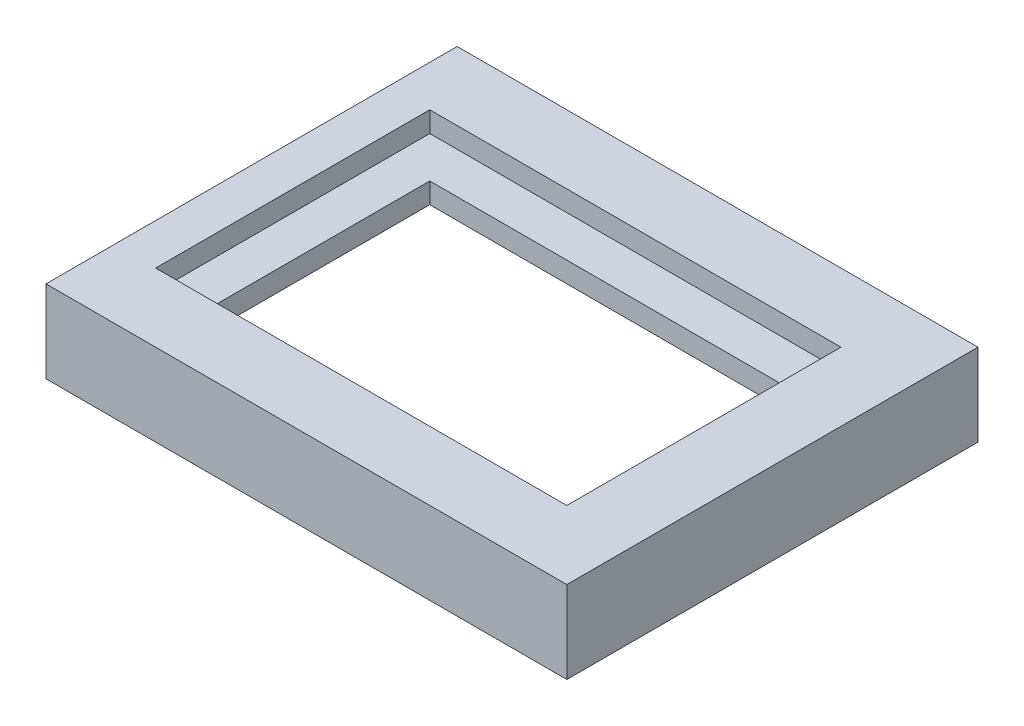
SolidWorks part; units mm, degrees
ref_plane "Front Plane" through (0, 0, 0) normal (0, 0, 1) x (1, 0, 0)
ref_plane "Top Plane" through (0, 0, 0) normal (0, 1, 0) x (1, 0, 0)
ref_plane "Right Plane" through (0, 0, 0) normal (1, 0, 0) x (0, 0, -1)
sketch "Sketch1" plane through (0, 0, 0) normal (0, 1, 0) x (1, 0, 0)
  line L1 (-9, -6.5) -> (9, -6.5)
  line L2 (-9, -6.5) -> (-9, 6.5)
  line L3 (-9, 6.5) -> (9, 6.5)
  line L4 (9, -6.5) -> (9, 6.5)
  line L5 (-9, -6.5) -> (9, 6.5) construction
  line L6 (-9, 6.5) -> (9, -6.5) construction
  line L7 (-10, -7.5) -> (10, -7.5)
  line L8 (-10, -7.5) -> (-10, 7.5)
  line L9 (-10, 7.5) -> (10, 7.5)
  line L10 (10, -7.5) -> (10, 7.5)
  line L11 (-10, -7.5) -> (10, 7.5) construction
  line L12 (-10, 7.5) -> (10, -7.5) construction
  point P0 (0, 0)
  point P6 (0, 0)
  dimension "D1" = 18
  dimension "D2" = 13
  dimension "D3" = 20
  dimension "D4" = 15
extrude "Boss-Extrude3" add sketch "Sketch1" along normal blind 3 contours L7 L10 L9 L8
sketch "Sketch4" plane through (-10, 0, 0) normal (-1, 0, 0) x (0, 0, 1)
  line L0 (-7.5, 1.5) -> (7.5, 1.5)
  line L1 (-7.5, 3) -> (-7.5, 0) construction
  line L2 (7.5, 3) -> (7.5, 0) construction
  line L4 (-6.5, 0.75) -> (6.5, 0.75)
  line L5 (-6.5, 0.75) -> (-6.5, 2.25)
  line L6 (-6.5, 2.25) -> (6.5, 2.25)
  line L7 (6.5, 0.75) -> (6.5, 2.25)
  line L8 (-6.5, 0.75) -> (6.5, 2.25) construction
  line L9 (-6.5, 2.25) -> (6.5, 0.75) construction
  point P6 (0, 1.5)
  dimension "D1" = 1.5
  dimension "D2" = 13
extrude "Cut-Extrude1" cut sketch "Sketch4" against normal blind 18 contours L5 L6 L7 L4
sketch "Sketch5" plane through (0, 3, 0) normal (0, 1, 0) x (1, 0, 0)
  line L0 (-10, 7.5) -> (-10, 6.5)
  line L1 (-10, -7.5) -> (-10, 7.5) construction
  line L2 (-1, 6.5) -> (-1, -6.5)
  line L3 (-10, 6.5) -> (8, 6.5)
  line L4 (-10, 6.5) -> (-10, -6.5)
  line L5 (-10, -6.5) -> (8, -6.5)
  line L6 (8, 6.5) -> (8, -6.5)
  line L7 (8, 6.5) -> (8, 7.5)
  line L8 (-8.5, -5) -> (6.5, -5)
  line L9 (-8.5, -5) -> (-8.5, 5)
  line L10 (-8.5, 5) -> (6.5, 5)
  line L11 (6.5, -5) -> (6.5, 5)
  line L12 (-8.5, -5) -> (6.5, 5) construction
  line L13 (-8.5, 5) -> (6.5, -5) construction
  line L14 (-10, 7.5) -> (10, 7.5) construction
  line L15 (8, 7.5) -> (8, -7.5)
  line L16 (-10, -7.5) -> (10, -7.5) construction
  line L18 (8, 7.5) -> (9, 7.5)
  line L19 (8, 7.5) -> (8, -7.5)
  line L20 (8, -7.5) -> (9, -7.5)
  line L21 (9, 7.5) -> (9, -7.5)
  line L22 (9, 7.5) -> (10, 7.5)
  line L23 (9, 7.5) -> (9, -7.5)
  line L24 (9, -7.5) -> (10, -7.5)
  line L25 (10, 7.5) -> (10, -7.5)
  point P10 (-1, 0)
  line M7 (-10, -7.5) -> (10, -7.5)
  line M8 (10, -7.5) -> (10, 7.5)
  line M9 (10, 7.5) -> (-10, 7.5)
  dimension "D1" = 18
  dimension "D2" = 1
  dimension "D3" = 13
  dimension "D4" = 10
  dimension "D5" = 15
  dimension "D6" = 1
extrude "Cut-Extrude2" cut sketch "Sketch5" against normal blind 18 contours L10 L9 L8 L2 | L8 L11 L10 L2 region at (2.75, 3, 0) region at (-4.75, 3, 0)
extrude "Cut-Extrude3" cut sketch "Sketch5<3>" against normal blind 18 contours L21 M9 M7 M8 region at (9.5, 3, 0)
sketch "Sketch5<3>" plane through (0, 3, 0) normal (0, 1, 0) x (1, 0, 0) same geometry as "Sketch5"
